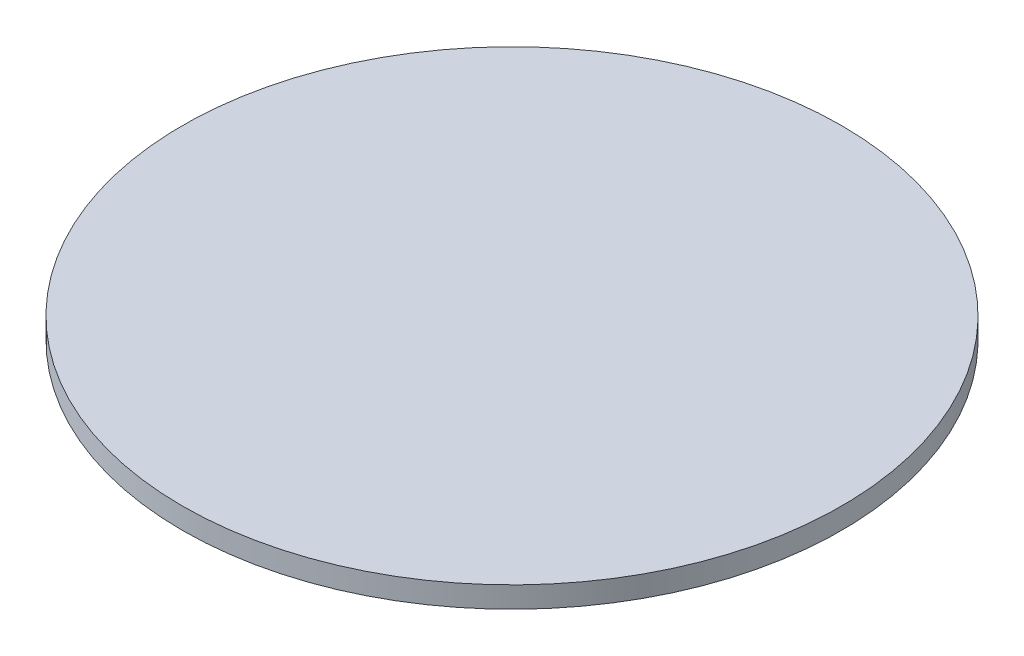
SolidWorks part; units mm, degrees
ref_plane "Front Plane" through (0, 0, 0) normal (0, 0, 1) x (1, 0, 0)
ref_plane "Top Plane" through (0, 0, 0) normal (0, 1, 0) x (1, 0, 0)
ref_plane "Right Plane" through (0, 0, 0) normal (1, 0, 0) x (0, 0, -1)
sketch "Sketch1" plane through (0, 0, 0) normal (0, 1, 0) x (1, 0, 0)
  circle A0 centre (0, 0) radius 49.53
  dimension "D1" = 99.06
extrude "Boss-Extrude1" add sketch "Sketch1" along normal blind 3.175
